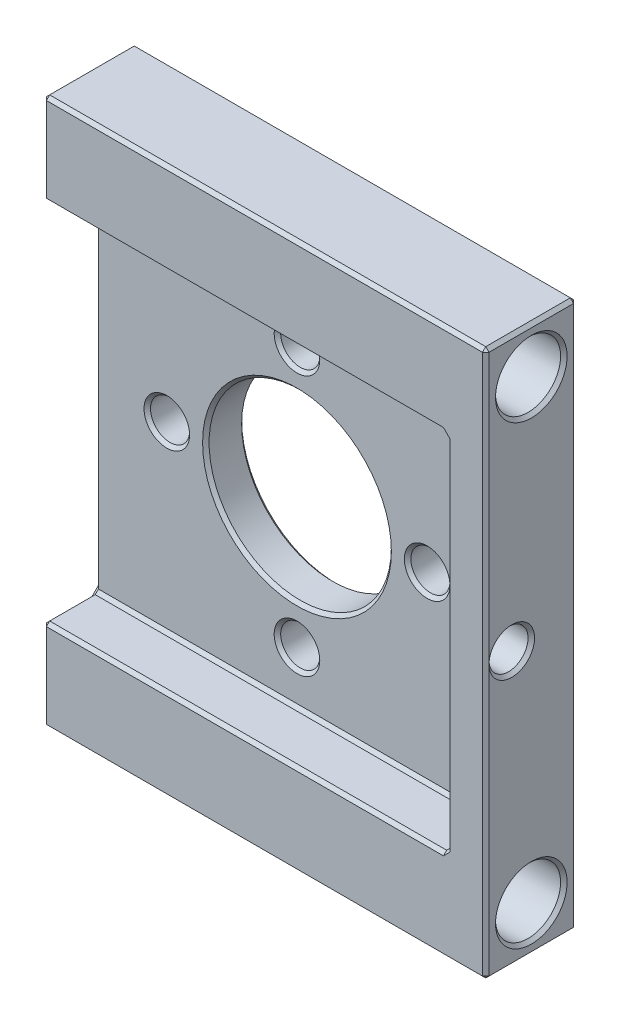
SolidWorks part; units mm, degrees
ref_plane "Plan de face" through (0, 0, 0) normal (0, 0, 1) x (1, 0, 0)
ref_plane "Plan de dessus" through (0, 0, 0) normal (0, 1, 0) x (1, 0, 0)
ref_plane "Plan de droite" through (0, 0, 0) normal (1, 0, 0) x (0, 0, -1)
sketch "Esquisse1" plane through (0, 0, 0) normal (0, 0, 1) x (1, 0, 0)
  line L1 (0, 0) -> (34, 0)
  line L2 (0, 0) -> (0, 42)
  line L3 (0, 42) -> (34, 42)
  line L4 (34, 0) -> (34, 42)
  dimension "D1" = 42
  dimension "D2" = 34
extrude "Boss.-Extru.1" add sketch "Esquisse1" along normal blind 7
sketch "Esquisse2" plane through (0, 0, 7) normal (0, 0, 1) x (1, 0, 0)
  line L0 (0, 42) -> (0, 0) construction
  line L1 (0, 35) -> (31, 35)
  line L2 (0, 35) -> (0, 7)
  line L3 (0, 7) -> (31, 7)
  line L4 (31, 35) -> (31, 7)
  line L5 (34, 0) -> (34, 42) construction
  line L6 (34, 42) -> (0, 42) construction
  line L7 (0, 0) -> (34, 0) construction
  dimension "D1" = 3
  dimension "D2" = 7
  dimension "D3" = 7
extrude "Enlèv. mat.-Extru.1" cut sketch "Esquisse2" against normal blind 4
sketch "Esquisse3" plane through (0, 0, 0) normal (-1, 0, 0) x (0, 0, 1)
  line L0 (3.5, 42) -> (3.5, 0) construction
  line L1 (7, 42) -> (0, 42) construction
  line L2 (7, 0) -> (0, 0) construction
  line L3 (0, 42) -> (7, 35) construction
  line L4 (7, 42) -> (7, 35) construction
  line L5 (7, 7) -> (0, 0) construction
  circle A0 centre (3.5, 38.5) radius 2.5
  circle A1 centre (3.5, 3.5) radius 2.5
  dimension "D1" = 5
  dimension "D2" = 5
extrude "Enlèv. mat.-Extru.2" cut sketch "Esquisse3" against normal through all
sketch "Esquisse4" plane through (0, 0, 3) normal (0, 0, 1) x (1, 0, 0)
  line L0 (15.5, 21) -> (15.5, 31) construction
  line L1 (15.5, 11) -> (15.5, 21) construction
  line L2 (15.5, 21) -> (25.5, 21) construction
  line L3 (15.5, 21) -> (5.5, 21) construction
  line L4 (0, 35) -> (31, 7) construction
  circle A0 centre (15.5, 21) radius 7
  circle A1 centre (15.5, 31) radius 1.5
  circle A2 centre (15.5, 11) radius 1.5
  circle A3 centre (25.5, 21) radius 1.5
  circle A4 centre (5.5, 21) radius 1.5
  dimension "D1" = 3
  dimension "D2" = 3
  dimension "D3" = 3
  dimension "D4" = 14
  dimension "D5" = 3
  dimension "D6" = 90
  dimension "D7" = 10
  dimension "D8" = 90
  dimension "D9" = 90
extrude "Enlèv. mat.-Extru.3" cut sketch "Esquisse4" against normal blind 4
sketch "Esquisse5" plane through (34, 0, 0) normal (1, 0, 0) x (0, 0, -1)
  line L0 (-3, 35) -> (-7, 7) construction
  circle A0 centre (-5, 21) radius 1.5
  dimension "D1" = 3
extrude "Enlèv. mat.-Extru.4" cut sketch "Esquisse5" against normal blind 4
chamfer "Chanfrein2" distance 0.25 angle 45 40 edges at (0, 0, 3.5) (34, 0, 3.5) (34, 42, 3.5) (17, 42, 0) (34, 21, 0) (17, 0, 0) (0, 21, 0) (0, 42, 3.5) (17, 42, 7) (34, 21, 7) (17, 0, 7) (0, 38.5, 7) (0, 3.5, 7) (0, 35, 5) (31, 35, 5) (31, 7, 5) (15.5, 35, 3) (31, 21, 3) (15.5, 7, 3) (0, 21, 3) (0, 7, 5) (15.5, 35, 7) (31, 21, 7) (15.5, 7, 7) (34, 38.5, 6) (0, 38.5, 6) (34, 3.5, 6) (0, 3.5, 6) (14, 31, 0) (14, 11, 0) (24, 21, 0) (4, 21, 0) (8.5, 21, 0) (22.5, 21, 3) (17, 31, 3) (17, 11, 3) (27, 21, 3) (7, 21, 3) (31, 22.5, 5) (34, 22.5, 5)
